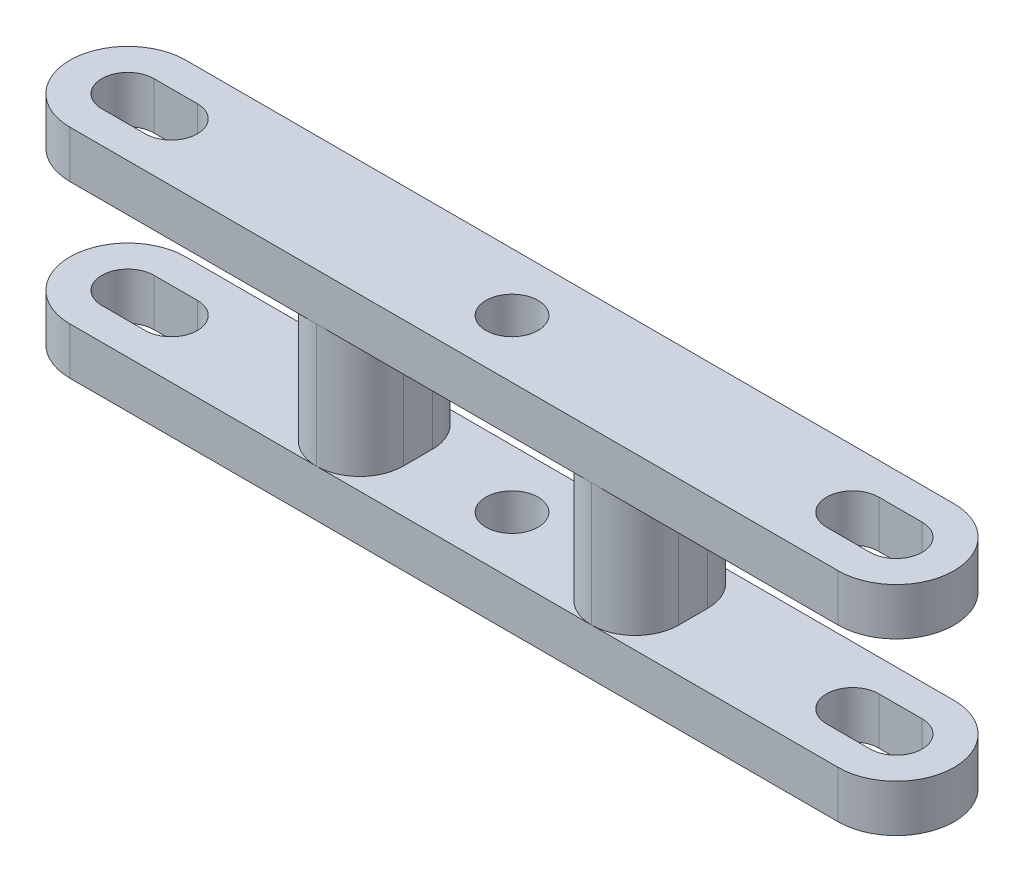
SolidWorks part; units mm, degrees
ref_plane "Front Plane" through (0, 0, 0) normal (0, 0, 1) x (1, 0, 0)
ref_plane "Top Plane" through (0, 0, 0) normal (0, 1, 0) x (1, 0, 0)
ref_plane "Right Plane" through (0, 0, 0) normal (1, 0, 0) x (0, 0, -1)
sketch "Sketch1" plane through (0, 0, 0) normal (0, 1, 0) x (1, 0, 0)
  line L0 (33.655, 0) -> (-33.655, 0) construction
  line L1 (-33.655, 0) -> (-29.845, 0) construction
  line L2 (33.655, -5.08) -> (-33.655, -5.08)
  line L3 (33.655, 5.08) -> (-33.655, 5.08)
  line L6 (33.655, 0) -> (29.845, 0) construction
  line L7 (33.655, -2.286) -> (29.845, -2.286)
  line L8 (33.655, 2.286) -> (29.845, 2.286)
  line L9 (-33.655, 2.286) -> (-29.845, 2.286)
  line L10 (-33.655, -2.286) -> (-29.845, -2.286)
  arc A0 (33.655, -5.08) -> (33.655, 5.08) centre (33.655, 0) ccw
  arc A1 (-33.655, 5.08) -> (-33.655, -5.08) centre (-33.655, 0) ccw
  arc A6 (33.655, -2.286) -> (33.655, 2.286) centre (33.655, 0) ccw
  arc A7 (29.845, 2.286) -> (29.845, -2.286) centre (29.845, 0) ccw
  circle A8 centre (0, 0) radius 2.286
  arc A9 (-33.655, 2.286) -> (-33.655, -2.286) centre (-33.655, 0) ccw
  arc A10 (-29.845, -2.286) -> (-29.845, 2.286) centre (-29.845, 0) ccw
  point P5 (0, 0)
  point P12 (-31.75, 0)
  point P19 (31.75, 0)
  dimension "D5" = 4.572
  dimension "D6" = 3.81
  dimension "D1" = 4.572
  dimension "D2" = 4.572
  dimension "D3" = 10.16
  dimension "D4" = 67.31
  dimension "D7" = 3.81
extrude "Boss-Extrude1" add sketch "Sketch1" along normal mid plane 19.05
sketch "Sketch3" plane through (0, 0, 5.08) normal (0, 0, 1) x (1, 0, 0)
  line L0 (-38.735, 9.525) -> (-38.735, -9.525) construction
  line L1 (-38.735, 5.3975) -> (-15.875, 5.3975)
  line L2 (-38.735, 5.3975) -> (-38.735, -5.3975)
  line L3 (-38.735, -5.3975) -> (-15.875, -5.3975)
  line L4 (-15.875, 5.3975) -> (-15.875, -5.3975)
  line L5 (0, 9.525) -> (0, -9.525) construction
  line L6 (8.255, -5.3975) -> (-8.255, -5.3975)
  line L7 (8.255, -5.3975) -> (8.255, 5.3975)
  line L8 (8.255, 5.3975) -> (-8.255, 5.3975)
  line L9 (-8.255, -5.3975) -> (-8.255, 5.3975)
  line L10 (8.255, -5.3975) -> (-8.255, 5.3975) construction
  line L11 (8.255, 5.3975) -> (-8.255, -5.3975) construction
  line L12 (-33.655, 9.525) -> (33.655, 9.525) construction
  line L13 (-33.655, -9.525) -> (33.655, -9.525) construction
  line L14 (15.875, 5.3975) -> (15.875, -5.3975)
  line L15 (38.735, -5.3975) -> (15.875, -5.3975)
  line L16 (38.735, 5.3975) -> (38.735, -5.3975)
  line L17 (38.735, 5.3975) -> (15.875, 5.3975)
  point P4 (-38.735, 0)
  point P9 (0, 0)
  point P19 (38.735, 0)
  dimension "D1" = 22.86
  dimension "D2" = 10.795
  dimension "D3" = 16.51
extrude "Cut-Extrude1" cut sketch "Sketch3" against normal through all
fillet "Fillet1" radius 3.81 8 edges at (15.875, 0, -5.08) (15.875, 0, 5.08) (8.255, 0, -5.08) (8.255, 0, 5.08) (-8.255, 0, -5.08) (-8.255, 0, 5.08) (-15.875, 0, 5.08) (-15.875, 0, -5.08)
